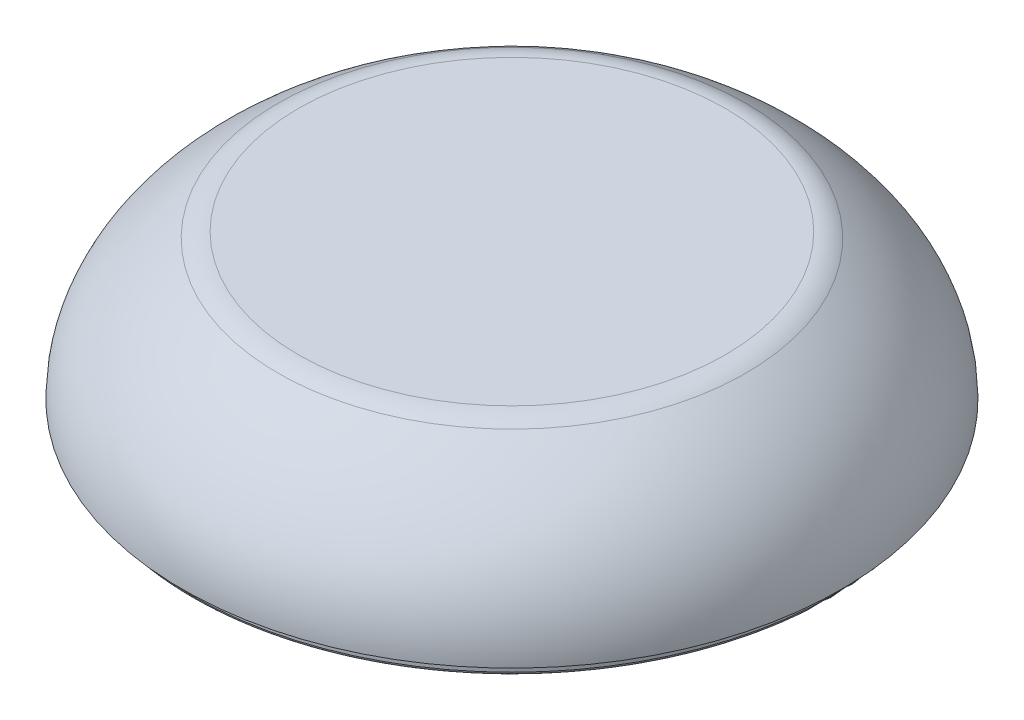
SolidWorks part; units mm, degrees
ref_plane "Plano frontal" through (0, 0, 0) normal (0, 0, 1) x (1, 0, 0)
ref_plane "Plano superior" through (0, 0, 0) normal (0, 1, 0) x (1, 0, 0)
ref_plane "Plano direito" through (0, 0, 0) normal (1, 0, 0) x (0, 0, -1)
sketch "Esboço3" plane through (0, 0, 0) normal (0, 0, 1) x (1, 0, 0)
  line L2 (0, 0) -> (0, 22)
  line L3 (0, 22) -> (33.9935, 22)
  line L4 (0, 0) -> (50, 0)
  ellipse E0 centre (0, 0) end of major axis (-50, 0) minor radius 30 (50, 0) -> (33.9935, 22) ccw
  dimension "D1" = 30
  dimension "D2" = 100
revolve "Revolução2" add sketch "Esboço3" angle 360 about L2
shell "Casca1" thickness 2 removed face at (0, 0, -50)
sketch "Esboço4" plane through (0, 0, 0) normal (0, -1, 0) x (1, 0, 0)
  circle A0 centre (0, 0) radius 48.5
  circle A1 centre (0, 0) radius 47
  dimension "D1" = 94
  dimension "D2" = 97
extrude "Ressalto-extrusão1" add sketch "Esboço4" against normal up to next and the other way blind 2
fillet "Filete1" radius 10 1 edges at (0, 5.6318, -47)
fillet "Filete2" radius 0.4 1 edges at (0, -2, -48.5)
fillet "Filete4" radius 6 1 edges at (0, 22, -33.9935)
